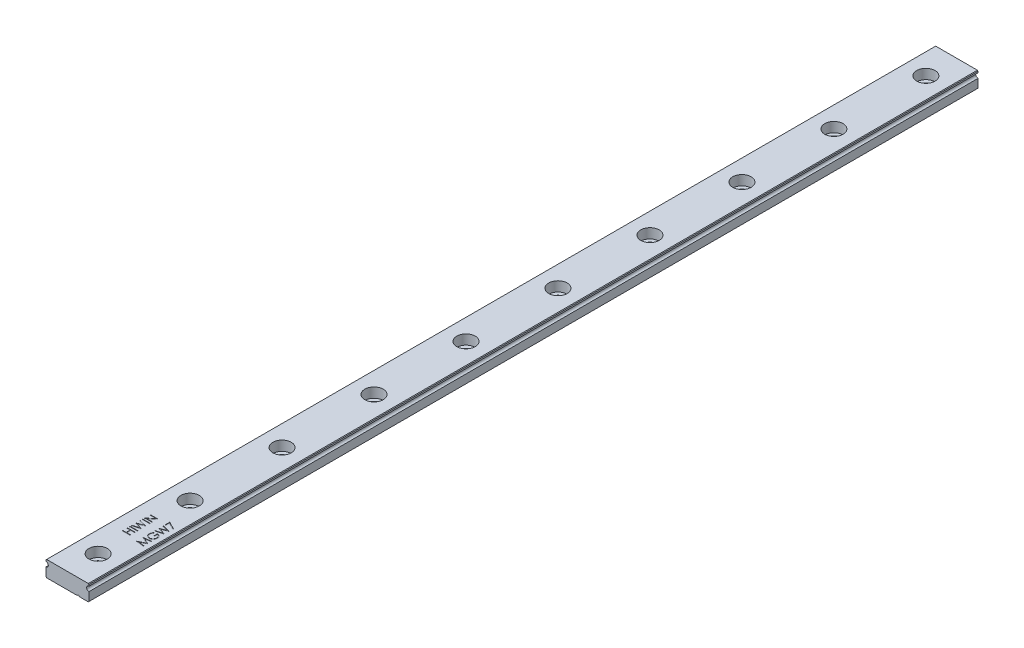
SolidWorks part; units mm, degrees
material "镀铬不锈钢"
ref_plane "前视基准面" through (0, 0, 0) normal (0, 0, 1) x (1, 0, 0)
ref_plane "上视基准面" through (0, 0, 0) normal (0, 1, 0) x (1, 0, 0)
ref_plane "右视基准面" through (0, 0, 0) normal (1, 0, 0) x (0, 0, -1)
sketch "草图1" plane through (0, 0, 0) normal (0, 0, 1) x (1, 0, 0)
  line L12 (6.8, 5.2) -> (-6.8, 5.2)
  line L13 (7, 4.5) -> (7, 5)
  line L14 (-7, 0.2) -> (-6.8, 0)
  line L15 (3.8, 0) -> (6.8, 0)
  line L16 (7, 0.2) -> (7, 3)
  line L17 (0, 5.2) -> (0, 0) construction
  line L18 (-6.8, 0) -> (3.2, 0)
  line L19 (-6.8, 5.2) -> (-7, 5)
  line L20 (-7, 5) -> (-7, 4.5)
  line L21 (7, 5) -> (6.8, 5.2)
  line L22 (6.8, 0) -> (7, 0.2)
  line L23 (-7, 3) -> (-7, 0.2)
  arc A3 (-7, 3) -> (-7, 4.5) centre (-7, 3.75) ccw
  arc A4 (3.8, 0) -> (3.2, 0) centre (3.5, 0) ccw
  arc A5 (7, 4.5) -> (7, 3) centre (7, 3.75) ccw
extrude "凸台-拉伸1" add sketch "草图1" against normal blind 290
hole_wizard "M3 六角凹头螺钉的柱形沉头孔1" positions "草图3" profile "草图2" counterbore size "M3" standard "ISO" end condition through all
sketch "草图3" plane through (-1.5973, 5.2, -94.5605) normal (0, 1, 0) x (-1, 0, 0)
  line L6 (-8.3973, 94.5605) -> (5.2027, 94.5605) construction
  point P15 (-1.5973, 84.5605)
  dimension "D1" = 10
sketch "草图2" plane through (0, 5.2, -10) normal (1, 0, 0) x (0, 0, 1)
  line L0 (0, 0) -> (0, 5.2)
  line L1 (0, 5.2) -> (1.75, 5.2)
  line L3 (1.75, 5.2) -> (1.75, 3.2)
  line L4 (1.75, 3.2) -> (3, 3.2)
  line L5 (3, 3.2) -> (3, 0)
  line L7 (3, 0) -> (0, 0)
  line L11 (0, -6.35) -> (0, 107.95) construction
  dimension "通孔孔直径" = 3.5
  dimension "通孔孔深度" = 5.2
  dimension "柱形沉头孔直径" = 6
  dimension "柱形沉头孔深度" = 3.2
pattern_linear "阵列(线性)1" count 10 spacing 30 along (0, 0, -1) of "M3 六角凹头螺钉的柱形沉头孔1"
sketch "草图4" plane through (0, 5.2, 0) normal (0, 1, 0) x (1, 0, 0)
  line L2 (0, 10) -> (0, 40) construction
  text T0 "HIWIN\r\nMGW7" font "Century Gothic" height 2.5
extrude "切除-拉伸1" cut sketch "草图4" against normal blind 0.1
equation "\"D1@凸台-拉伸1\" = 2 * \"D1@草图3\" + \"D3@阵列(线性)1\" *  (\"D1@阵列(线性)1\" - 1  ) "
